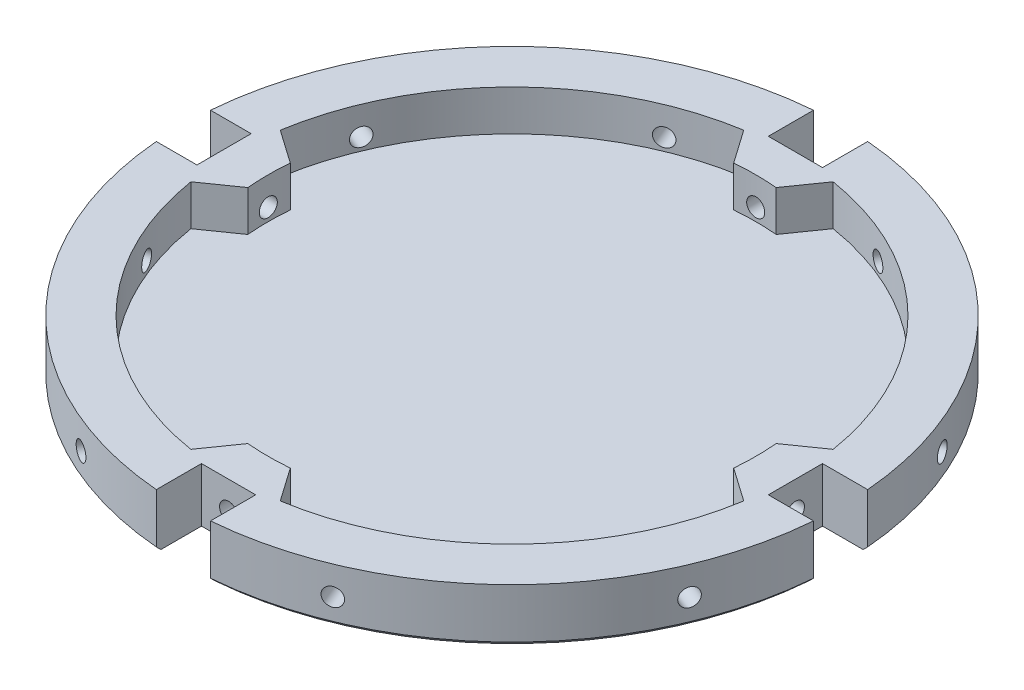
SolidWorks part; units mm, degrees
material "7075-T6, Piastra (SS)"
ref_plane "Piano frontale" through (0, 0, 0) normal (0, 0, 1) x (1, 0, 0)
ref_plane "Piano superiore" through (0, 0, 0) normal (0, 1, 0) x (1, 0, 0)
ref_plane "Piano destro" through (0, 0, 0) normal (1, 0, 0) x (0, 0, -1)
sketch "Schizzo1" plane through (0, 0, 0) normal (0, 0, 1) x (1, 0, 0)
  line L1 (-73, 24) -> (-62, 24)
  line L4 (0, 3) -> (0, 0)
  line L5 (0, 0) -> (-73, 0)
  line L7 (-73, 12) -> (-73, 0)
  line L10 (0, 0) -> (0, 105.2736) construction
  line L12 (-62, 3) -> (0, 3)
  line L13 (-73, 12) -> (-75, 12)
  line L14 (-75, 12) -> (-75, 14)
  line L15 (-75, 14) -> (-73, 14)
  line L16 (-73, 14) -> (-73, 24)
  line L19 (-62, 3) -> (-62, 0)
  line L20 (-62, 24) -> (-62, 3)
  dimension "D1" = 146
  dimension "D2" = 14
  dimension "D3" = 150
  dimension "D4" = 24
  dimension "D5" = 12
  dimension "D6" = 124
  dimension "D9" = 3
revolve "Rivoluzione1" add sketch "Schizzo1" angle 360 about L10
sketch "Schizzo2" plane through (0, 0, 0) normal (0, -1, 0) x (1, 0, 0)
  line L0 (0, 0) -> (-73, 0) construction
  line L1 (-72.753, 6) -> (-62.753, 6)
  line L2 (-62.753, 6) -> (-62.753, -6)
  line L3 (-62.753, -6) -> (-72.753, -6)
  circle A0 centre (0, 0) radius 73 construction
  arc A1 (-72.753, -6) -> (-72.753, 6) centre (0, 0) cw
  circle A2 centre (0, 0) radius 73 construction
  point P10 (-62.753, 0)
  dimension "D1" = 12
  dimension "D2" = 10
extrude "Taglio-Estrusione1" cut sketch "Schizzo2" against normal up to surface (12 mm away) up to face at (0, 12, -75)
sketch "Schizzo3" plane through (0, 24, 0) normal (0, 1, 0) x (1, 0, 0)
  line L0 (0, 0) -> (-73, 0) construction
  line L4 (0, 0) -> (-51.6188, 51.6188) construction
  line L7 (-43.8406, 43.8406) -> (-51.6188, 51.6188)
  line L8 (0, 0) -> (-67.4432, 27.9359) construction
  line L9 (0, 0) -> (-59.3078, 18.0717) construction
  line L10 (0, 0) -> (-54.7156, 29.1583) construction
  line L11 (-59.3078, 18.0717) -> (-69.8301, 21.278)
  line L12 (-54.7156, 29.1583) -> (-64.4232, 34.3315)
  line L13 (-59.3078, 18.0717) -> (-54.7156, 29.1583) construction
  line L14 (-62, 0) -> (-73, 0)
  circle A2 centre (0, 0) radius 62 construction
  arc A5 (-59.3078, 18.0717) -> (-43.8406, 43.8406) centre (0, 0) cw
  circle A6 centre (0, 0) radius 73 construction
  arc A7 (-69.8301, 21.278) -> (-51.6188, 51.6188) centre (0, 0) cw
  arc A8 (-69.8301, 21.278) -> (-64.4232, 34.3315) centre (0, 0) cw
  arc A9 (-62, 0) -> (-59.3078, 18.0717) centre (0, 0) cw
  arc A10 (-73, 0) -> (-69.8301, 21.278) centre (0, 0) cw
  point P19 (-57.0117, 23.615)
  dimension "D2" = 45
  dimension "D1" = 22.5
  dimension "D4" = 12
extrude "Taglio-Estrusione3" cut sketch "Schizzo3" against normal up to surface (10 mm away)
hole_wizard "Foro Ø4.0 (4)-1" positions "Schizzo3D1" profile "Schizzo5" hole size "Ø4.0" standard "ISO"
sketch3d "Schizzo3D1"
  point P0 (-67.4812, 18.5213, -27.8441)
sketch "Schizzo5" plane through (-67.4812, 18.5213, -27.8441) normal (0, 1, 0) x (-0.3814, 0, 0.9244)
  line L0 (0, 0) -> (0, 19)
  line L1 (0, 19) -> (2, 17.7983)
  line L2 (2, 17.7983) -> (2, 0)
  line L5 (2, 0) -> (0, 0)
  line L10 (0, 19) -> (-2, 17.7983) construction
  line L11 (0, -6.35) -> (0, 107.95) construction
  dimension "Hole Dia." = 4
  dimension "Hole Depth" = 19
  dimension "Drill Angle" = 118
hole_wizard "Foro Ø4.0 (4)-2" positions "Schizzo6" profile "Schizzo7" hole size "Ø4.0" standard "ISO"
sketch "Schizzo6" plane through (-62.753, 0, 0) normal (-1, 0, 0) x (0, 0, 1)
  point P0 (0, 5.7708)
sketch "Schizzo7" plane through (-62.753, 5.7708, 0) normal (0, 1, 0) x (0, 0, 1)
  line L0 (0, 0) -> (0, 19)
  line L1 (0, 19) -> (2, 17.7983)
  line L2 (2, 17.7983) -> (2, 0)
  line L5 (2, 0) -> (0, 0)
  line L10 (0, 19) -> (-2, 17.7983) construction
  line L11 (0, -6.35) -> (0, 107.95) construction
  dimension "Hole Dia." = 4
  dimension "Hole Depth" = 19
  dimension "Drill Angle" = 118
chamfer "Smusso1" distance 1 angle 45 1 edges at (73, 0, 0)
chamfer "Smusso2" distance 1 angle 45 1 edges at (-62.753, 0, 0)
fillet "Raccordo1" radius 1 1 edges at (-62.753, 12, 0)
chamfer "Smusso3" distance 1 angle 45 1 edges at (-67.4432, 24, -27.9359)
pattern_circular "RipetizioneCircolare5" count 8 over 360 about axis through (0, 0, 0) along (0, 1, 0) of "Foro Ø4.0 (4)-1", "Smusso3", "Taglio-Estrusione3"
pattern_circular "RipetizioneCircolare6" count 4 over 360 of "Taglio-Estrusione1", "Foro Ø4.0 (4)-2", "Raccordo1", "Smusso2"
hole_wizard "Foro Ø4.0 (4)-3" positions "Schizzo3D3" profile "Schizzo9" hole size "Ø4.0" standard "ISO"
sketch3d "Schizzo3D3"
  point P0 (-67.4973, 5.7088, 27.805)
  point P2 (-67.4973, 5.7088, 27.805)
sketch "Schizzo9" plane through (-67.4973, 5.7088, 27.805) normal (0, 1, 0) x (0.3809, 0, 0.9246)
  line L0 (0, 0) -> (0, 19)
  line L1 (0, 19) -> (2, 17.7983)
  line L2 (2, 17.7983) -> (2, 0)
  line L5 (2, 0) -> (0, 0)
  line L10 (0, 19) -> (-2, 17.7983) construction
  line L11 (0, -6.35) -> (0, 107.95) construction
  dimension "Hole Dia." = 4
  dimension "Hole Depth" = 19
  dimension "Drill Angle" = 118
pattern_circular "RipetizioneCircolare7" count 8 over 360 about axis through (0, 1, 0) along (0, -1, 0) of "Foro Ø4.0 (4)-3"
sketch "Schizzo10" [suppressed] plane through (0, 3, 0) normal (0, 1, 0) x (1, 0, 0)
  circle A0 centre (0, 0) radius 62
  arc A1 (-29.1583, 54.7156) -> (-54.7156, 29.1583) centre (0, 0) ccw construction
extrude "Taglio-Estrusione4" [suppressed] cut sketch "Schizzo10" against normal blind 10
sketch "Schizzo11" plane through (0, 3, 0) normal (0, 1, 0) x (1, 0, 0)
  line L0 (-4.7064, 53.7945) -> (-5.4037, 61.7641)
  line L1 (0, 54) -> (0, 0) construction
  line L2 (4.7064, 53.7945) -> (5.4037, 61.7641)
  line L3 (-4.7064, 53.7945) -> (0, 0) construction
  line L4 (0, 0) -> (4.7064, 53.7945) construction
  arc A0 (18.0717, 59.3078) -> (-18.0717, 59.3078) centre (0, 0) ccw construction
  arc A1 (-4.7064, 53.7945) -> (4.7064, 53.7945) centre (0, 0) cw
  arc A3 (-5.4037, 61.7641) -> (5.4037, 61.7641) centre (0, 0) cw
  circle M4 centre (0, 0) radius 62
  dimension "D1" = 54
  dimension "D2" = 10
extrude "Estrusione-Estrusione1" add sketch "Schizzo11" along a picked direction on the side of the normal blind 11 contours L0 A1 L2 M4
pattern_circular "RipetizioneCircolare8" count 4 over 360 about axis through (0, 0, 0) along (0, -1, 0) of "Estrusione-Estrusione1"
sketch "Schizzo12" plane through (-62.753, 0, 0) normal (-1, 0, 0) x (0, 0, 1)
  circle A0 centre (0, 5.7708) radius 2
  circle A1 centre (0, 5.7708) radius 2 construction
extrude "Taglio-Estrusione5" cut sketch "Schizzo12" against normal blind 10
pattern_circular "RipetizioneCircolare9" count 4 over 360 about axis through (0, 0, 0) along (0, 1, 0) of "Taglio-Estrusione1", "Foro Ø4.0 (4)-2"
sketch "Schizzo13" plane through (0, 24, 0) normal (0, 1, 0) x (1, 0, 0)
  circle A0 centre (0, 0) radius 75
extrude "Taglio-Estrusione6" cut sketch "Schizzo13" against normal up to surface (12 mm away)
chamfer "Smusso4" distance 8 angle 30 2 edges at (-61.7641, 7.5, 5.4037) (-61.7641, 7.5, -5.4037)
chamfer "Smusso5" distance 8 angle 30 6 edges at (61.7641, 7.5, -5.4037) (5.4037, 7.5, 61.7641) (-5.4037, 7.5, 61.7641) (61.7641, 7.5, 5.4037) (5.4037, 7.5, -61.7641) (-5.4037, 7.5, -61.7641)
